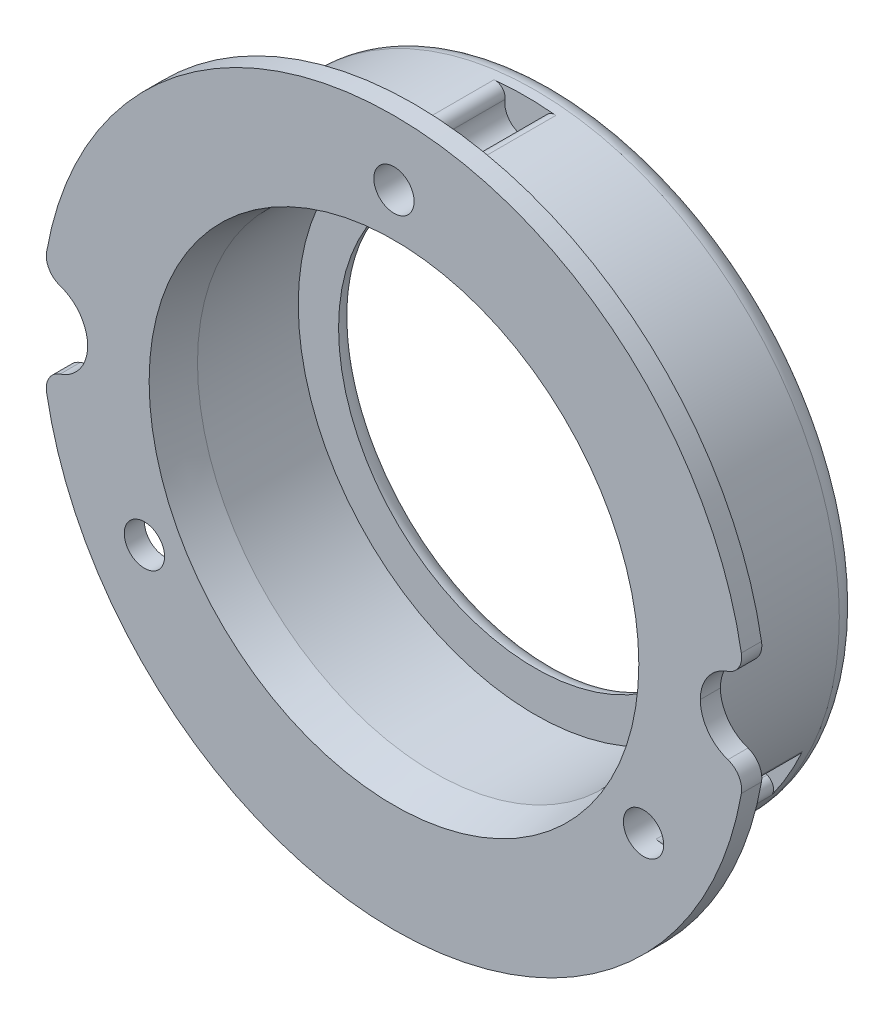
SolidWorks part; units mm, degrees
ref_plane "前视基准面" through (0, 0, 0) normal (0, 0, 1) x (1, 0, 0)
ref_plane "上视基准面" through (0, 0, 0) normal (0, 1, 0) x (1, 0, 0)
ref_plane "右视基准面" through (0, 0, 0) normal (1, 0, 0) x (0, 0, -1)
sketch "草图1" plane through (0, 0, 0) normal (0, 0, 1) x (1, 0, 0)
  circle A0 centre (0, 0) radius 15.1
  circle A1 centre (0, 0) radius 11.75
  dimension "D1" = 23.5
  dimension "D2" = 30.2
extrude "凸台-拉伸1" add sketch "草图1" along normal mid plane 7
sketch "草图2" plane through (0, 0, -3.5) normal (0, 0, -1) x (-1, 0, 0)
  circle A0 centre (0, 0) radius 11.75
  circle A1 centre (0, 0) radius 11.75 construction
  circle A2 centre (0, 0) radius 9.75
  dimension "D1" = 2
extrude "凸台-拉伸2" add sketch "草图2" against normal blind 1
fillet "圆角1" radius 1 1 edges at (15.1, 0, -3.5)
fillet "圆角2" radius 1 1 edges at (-9.75, 0, -3.5)
sketch "草图3" plane through (0, 0, 3.5) normal (0, 0, 1) x (1, 0, 0)
  circle A0 centre (0, 0) radius 11.75
  circle A1 centre (0, 0) radius 17.5
  dimension "D1" = 23.5
  dimension "D2" = 35
extrude "凸台-拉伸3" add sketch "草图3" along normal blind 1
sketch "草图4" plane through (0, 0, 3.5) normal (0, 0, -1) x (-1, 0, 0)
  line L0 (-23.6432, 0) -> (0, 0) construction
  line L1 (0, 0) -> (0, 22.776) construction
  line L3 (-20.0567, 2) -> (-15.0678, 2)
  line L4 (-20.0567, 2) -> (-20.0567, -2)
  line L5 (-20.0567, -2) -> (-15.0678, -2)
  arc A0 (-15.0678, 2) -> (-15.0678, -2) centre (0, 0) ccw
  dimension "D1" = 30.4
  dimension "D2" = 4
extrude "切除-拉伸1" cut sketch "草图4" against normal through all
mirror "镜向1" about plane through (0, 0, 0) normal (1, 0, 0) of "切除-拉伸1"
fillet "圆角3" radius 2 4 edges at (-15.0678, -2, 4) (-15.0678, 2, 4) (15.0678, -2, 4) (15.0678, 2, 4)
fillet "圆角4" radius 1 4 edges at (17.3853, 2, 4) (17.3853, -2, 4) (-17.3853, -2, 4) (-17.3853, 2, 4)
sketch "草图6" plane through (0, 0, 4.5) normal (0, 0, 1) x (1, 0, 0)
  line L0 (0, 20.0808) -> (0, 0) construction
  line L1 (0, 15.1) -> (3.1672, 15.1) construction
  circle A0 centre (0, 14.3) radius 1
  circle A1 centre (0, 0) radius 15.1 construction
  dimension "D1" = 2
  dimension "D2" = 0.2
extrude "切除-拉伸2" cut sketch "草图6" against normal blind 6.5
pattern_circular "阵列(圆周)2" count 3 every 120 about axis through (0, 0, 3.5) along (0, 0, -1) of "切除-拉伸2"
fillet "圆角6" radius 0.5 6 edges at (12.7579, -8.0775, 0.75) (13.3743, -7.0099, 0.75) (-12.7579, -8.0775, 0.75) (-13.3743, -7.0099, 0.75) (-0.6164, 15.0874, 0.75) (0.6164, 15.0874, 0.75)
chamfer "倒角1" distance 0.4 distance2 2 1 edges at (11.75, 0, 4.5) first distance on face at (-12.8842, -6.284, 4.5)
sketch "草图7" plane through (0, 0, -3.5) normal (0, 0, -1) x (-1, 0, 0)
  line L0 (-0.8535, 12.3799) -> (-0.6485, 12.3799)
  line L1 (-0.5585, 12.2899) -> (-0.5585, 11.1313)
  line L2 (-0.6485, 11.0413) -> (-0.8535, 11.0413)
  line L3 (-1.0335, 11.2213) -> (-1.0335, 12.1999)
  line L4 (-0.0233, 12.8515) -> (-0.4316, 12.3546)
  line L5 (-0.4316, 12.3546) -> (-0.4316, 11.0413)
  line L6 (-0.4316, 11.0413) -> (0.6752, 11.0413)
  line L7 (0.8475, 11.1691) -> (1.1366, 12.1224)
  line L8 (0.9643, 12.3546) -> (0.5297, 12.3546)
  line L9 (0.3497, 12.5346) -> (0.3497, 12.7583)
  line L10 (11.2382, -5.9703) -> (10.7965, -6.7353) construction
  line L11 (11.3141, -6.0141) -> (10.8724, -6.7792)
  line L12 (11.1622, -5.9264) -> (10.9899, -6.2248)
  line L13 (10.0329, -5.7837) -> (10.9414, -6.309) construction
  line L14 (10.0815, -5.6996) -> (10.7312, -6.0752)
  line L15 (9.9842, -5.8678) -> (10.6339, -6.2434)
  line L16 (10.5012, -5.5201) -> (10.9233, -5.7639) construction
  line L17 (10.5457, -5.4432) -> (10.7969, -5.5882)
  line L18 (10.4568, -5.5971) -> (10.6146, -5.6882)
  line L19 (10.8928, -6.3931) -> (10.7205, -6.6915)
  line L20 (9.9936, -6.398) -> (10.2441, -6.543)
  line L21 (10.0827, -6.2442) -> (10.2399, -6.3352)
  line L22 (10.0382, -6.3211) -> (10.46, -6.5653) construction
  line L23 (10.9034, -6.1748) -> (10.9899, -6.2248)
  line L24 (10.8062, -6.343) -> (10.8928, -6.3931)
  line L25 (-11.2083, -6.5694) -> (-11.1004, -6.5465)
  line L26 (-9.5267, -6.212) -> (-9.4189, -6.1891)
  line L27 (-11.2201, -6.3393) -> (-11.2939, -6.4212)
  line L28 (-10.3272, -6.8908) -> (-10.2721, -6.9863)
  line L29 (-9.9249, -5.241) -> (-9.9134, -5.1314)
  line L30 (-10.9715, -5.3196) -> (-11.0722, -5.2748)
  line L31 (-11.1867, -5.402) -> (-11.1316, -5.4975)
  line L32 (-10.0698, -5.0617) -> (-10.1436, -5.1437)
  line L33 (-9.401, -6.0189) -> (-9.5017, -5.974)
  line L34 (-10.1046, -6.9507) -> (-10.0931, -6.841)
  line L35 (-11.0387, -7.0195) -> (-11.4488, -7.3319)
  line L36 (-11.0387, -7.0195) -> (-11.2726, -7.4789)
  line L37 (-10.4793, -7.304) -> (-10.7789, -7.7706)
  line L38 (-10.4793, -7.304) -> (-10.5635, -7.8521)
  line L39 (-9.8573, -7.4419) -> (-10.0228, -7.9988)
  line L40 (-9.8573, -7.4419) -> (-9.793, -8.0193)
  line L41 (11.8482, -5.9304) -> (12.3238, -6.1293)
  line L42 (11.8482, -5.9304) -> (12.3631, -5.9032)
  line L43 (11.6678, -5.2863) -> (12.2217, -5.3125)
  line L44 (11.6678, -5.2863) -> (12.1846, -5.0852)
  line L45 (11.4762, -4.6787) -> (12.0413, -4.5436)
  line L46 (11.4762, -4.6787) -> (11.9441, -4.3343)
  line L47 (-0.5385, 13.0486) -> (-0.604, 13.56)
  line L48 (-0.5385, 13.0486) -> (-0.8194, 13.4809)
  line L49 (-1.0645, 12.7063) -> (-1.3189, 13.1991)
  line L50 (-1.0645, 12.7063) -> (-1.4971, 13.0534)
  line L51 (-1.495, 12.2367) -> (-1.8945, 12.6584)
  line L52 (-1.495, 12.2367) -> (-2.0272, 12.4697)
  line L53 (0, 0) -> (0, 18.4913) construction
  line L54 (0, 0) -> (14.9573, -8.6356) construction
  line L55 (0, 0) -> (-15.5885, -9) construction
  arc A0 (-0.0233, 12.8515) -> (0.3497, 12.7583) centre (0.1398, 12.7113) cw
  circle A1 centre (10.5364, -6.0744) radius 1.107
  arc A2 (11.3141, -6.0141) -> (11.1622, -5.9264) centre (11.2382, -5.9703) ccw
  arc A3 (10.7205, -6.6915) -> (10.8724, -6.7792) centre (10.7965, -6.7353) ccw
  arc A4 (10.0815, -5.6996) -> (9.9842, -5.8678) centre (10.0329, -5.7837) ccw
  arc A5 (9.9936, -6.398) -> (10.0827, -6.2442) centre (10.0382, -6.3211) cw
  arc A6 (10.5457, -5.4432) -> (10.4568, -5.5971) centre (10.5012, -5.5201) ccw
  arc A7 (10.6146, -5.6882) -> (10.7312, -6.0752) centre (10.3636, -5.9748) cw
  arc A8 (10.7969, -5.5882) -> (10.9034, -6.1748) centre (10.3572, -5.9711) cw
  arc A9 (10.6339, -6.2434) -> (10.2399, -6.3352) centre (10.3636, -5.9748) cw
  arc A10 (10.8062, -6.343) -> (10.2441, -6.543) centre (10.3572, -5.9711) cw
  arc A11 (-9.5267, -6.212) -> (-10.0931, -6.841) centre (-9.3771, -6.9163) ccw
  arc A12 (-9.9249, -5.241) -> (-9.5017, -5.974) centre (-9.2089, -5.3163) ccw
  arc A13 (-10.1436, -5.1437) -> (-10.9715, -5.3196) centre (-10.6786, -4.6619) cw
  arc A14 (-11.2201, -6.3393) -> (-11.1316, -5.4975) centre (-11.7552, -5.8575) ccw
  arc A15 (-11.1004, -6.5465) -> (-10.3272, -6.8908) centre (-10.9507, -7.2508) cw
  arc A16 (-11.4488, -7.3319) -> (-11.2726, -7.4789) centre (-11.3775, -7.4255) ccw
  arc A17 (0.6752, 11.0413) -> (0.8475, 11.1691) centre (0.6752, 11.2213) ccw
  arc A18 (0.5297, 12.3546) -> (0.3497, 12.5346) centre (0.5297, 12.5346) cw
  arc A19 (1.1366, 12.1224) -> (0.9643, 12.3546) centre (0.9643, 12.1746) ccw
  arc A20 (-0.6485, 12.3799) -> (-0.5585, 12.2899) centre (-0.6485, 12.2899) cw
  arc A21 (-0.5585, 11.1313) -> (-0.6485, 11.0413) centre (-0.6485, 11.1313) cw
  arc A22 (-0.8535, 11.0413) -> (-1.0335, 11.2213) centre (-0.8535, 11.2213) cw
  arc A23 (-1.0335, 12.1999) -> (-0.8535, 12.3799) centre (-0.8535, 12.1999) cw
  arc A24 (-9.9134, -5.1314) -> (-10.0698, -5.0617) centre (-10.0029, -5.122) ccw
  arc A25 (-9.401, -6.0189) -> (-9.4189, -6.1891) centre (-9.4376, -6.1011) cw
  arc A26 (-10.1046, -6.9507) -> (-10.2721, -6.9863) centre (-10.1941, -6.9413) cw
  arc A27 (-11.2083, -6.5694) -> (-11.2939, -6.4212) centre (-11.227, -6.4814) cw
  arc A28 (-11.0722, -5.2748) -> (-11.1867, -5.402) centre (-11.1088, -5.357) ccw
  arc A29 (-10.7789, -7.7706) -> (-10.5635, -7.8521) centre (-10.6798, -7.8342) ccw
  arc A30 (-10.0228, -7.9988) -> (-9.793, -8.0193) centre (-9.91, -8.0323) ccw
  arc A31 (12.3238, -6.1293) -> (12.3631, -5.9032) centre (12.3692, -6.0207) ccw
  arc A32 (12.2217, -5.3125) -> (12.1846, -5.0852) centre (12.2273, -5.1949) ccw
  arc A33 (12.0413, -4.5436) -> (11.9441, -4.3343) centre (12.0139, -4.4291) ccw
  arc A34 (-0.604, 13.56) -> (-0.8194, 13.4809) centre (-0.7207, 13.545) ccw
  arc A35 (-1.3189, 13.1991) -> (-1.4971, 13.0534) centre (-1.4235, 13.1452) ccw
  arc A36 (-1.8945, 12.6584) -> (-2.0272, 12.4697) centre (-1.9799, 12.5775) ccw
  circle A37 centre (0, 0) radius 30 construction
  point P16 (11.0173, -6.3528)
  point P21 (10.4871, -6.0463)
  point P28 (10.7123, -5.642)
  dimension "D3" = 60
  dimension "D1" = 120
  dimension "D2" = 120
extrude "切除-拉伸3" [suppressed] cut sketch "草图7" against normal blind 0.5
